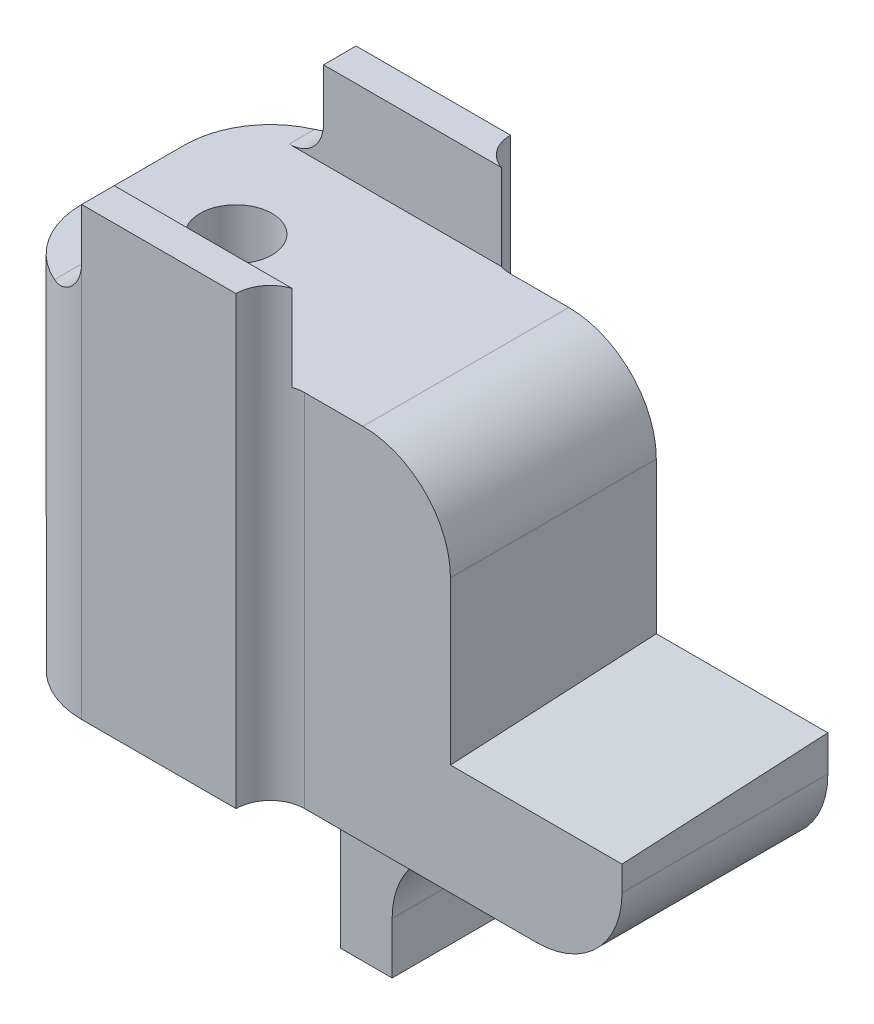
SolidWorks part; units mm, degrees
ref_plane "Front Plane" through (0, 0, 0) normal (0, 0, 1) x (1, 0, 0)
ref_plane "Top Plane" through (0, 0, 0) normal (0, 1, 0) x (1, 0, 0)
ref_plane "Right Plane" through (0, 0, 0) normal (1, 0, 0) x (0, 0, -1)
sketch "Sketch1" plane through (0, 0, 0) normal (0, 1, 0) x (1, 0, 0)
  line L5 (-6, 8) -> (6, 8)
  line L6 (-6, 8) -> (-6, -8)
  line L7 (-6, -8) -> (6, -8)
  line L8 (6, 8) -> (6, -8)
  line L9 (-6, 8) -> (6, -8) construction
  line L10 (-6, -8) -> (6, 8) construction
  line L11 (6, 8) -> (8, 8)
  line L12 (6, 8) -> (6, -8)
  line L13 (6, -8) -> (8, -8)
  line L14 (8, 8) -> (8, -8)
  circle A0 centre (0, 0) radius 2.1
  point P0 (0, 0)
  dimension "D1" = 4.2
  dimension "D2" = 16
  dimension "D3" = 6
  dimension "D4" = 2
extrude "Boss-Extrude1" add sketch "Sketch1" along normal blind 21 contours L8 L5 L6 L7 A0 | L14 L11 L8 L13 region at (0, 0, -7.8) region at (7, 0, 0)
fillet "Fillet1" radius 5 2 edges at (-6, 10.5, -8) (-6, 10.5, 8)
sketch "Sketch2" plane through (0, 21, 0) normal (0, 1, 0) x (1, 0, 0)
  line L0 (8, 0) -> (-6, 0) construction
  line L1 (8, 8) -> (-1, 8)
  line L2 (8, 8) -> (8, 6.1)
  line L3 (8, 6.1) -> (-1, 6.1)
  line L4 (-1, 8) -> (-1, 6.1)
  line L5 (8, 8) -> (8, -8) construction
  line L6 (-6, 3) -> (-6, -3) construction
  line L7 (-1, -8) -> (-1, -6.1)
  line L8 (8, -6.1) -> (-1, -6.1)
  line L9 (8, -8) -> (8, -6.1)
  line L10 (8, -8) -> (-1, -8)
  dimension "D1" = 1.9
extrude "Boss-Extrude2" add sketch "Sketch2" along normal blind 5
sketch "Sketch4" plane through (8, 0, 0) normal (1, 0, 0) x (0, 0, -1)
  line L0 (8, 26) -> (8, 0) construction
  line L1 (-6, 0) -> (6, 0)
  line L2 (-6, 0) -> (-6, 21)
  line L3 (-6, 21) -> (6, 21)
  line L4 (6, 0) -> (6, 21)
  line L6 (6.1, 21) -> (-6.1, 21) construction
  point P6 (0, 0)
  dimension "D1" = 2
extrude "Boss-Extrude3" add sketch "Sketch4" along normal offset from surface (10.5 mm away) 24.5 up to face at (-6, 10.5, 0)
fillet "Fillet2" radius 5.1 1 edges at (18.5, 21, 0)
fillet "Fillet4" radius 2 4 edges at (-1, 21, -7.05) (-1, 21, 7.05) (8, 10.5, -6) (8, 10.5, 6)
sketch "Sketch6" plane through (0, 0, 0) normal (0, -1, 0) x (1, 0, 0)
  line L5 (10.1, 4) -> (13.1, 4)
  line L6 (10.1, 4) -> (10.1, -4)
  line L7 (10.1, -4) -> (13.1, -4)
  line L8 (13.1, 4) -> (13.1, -4)
  point P4 (10.1, 0)
  dimension "D1" = 10.1
  dimension "D2" = 3
  dimension "D3" = 8
extrude "Boss-Extrude5" add sketch "Sketch6" along normal blind 8
fillet "Fillet6" radius 2 2 edges at (11.6, 0, -4) (11.6, 0, 4)
fillet "Fillet8" radius 5 1 edges at (13.1, 0, 0)
sketch "Sketch7" plane through (18.5, 0, 0) normal (1, 0, 0) x (0, 0, -1)
  line L0 (-6, 0) -> (-6, 6.45)
  line L2 (-6, 6.45) -> (6, 7.0789)
  line L4 (6, 7.0789) -> (6, 0)
  line L5 (6, 0) -> (-6, 0)
  line L6 (-6, 6.45) -> (6, 6.45) construction
  line L7 (-6, 15.9) -> (-6, 0) construction
  point P3 (0, 0)
  point P4 (0, 0)
  point P7 (0, 0)
  point P8 (-4.7691, 6.8401)
  point P11 (0, 0)
  point P12 (0, 0)
  dimension "D1" = 6.45
  dimension "D2" = 3
extrude "Boss-Extrude6" add sketch "Sketch7" along normal blind 10
fillet "Fillet9" radius 5 1 edges at (28.5, 0, 0)
